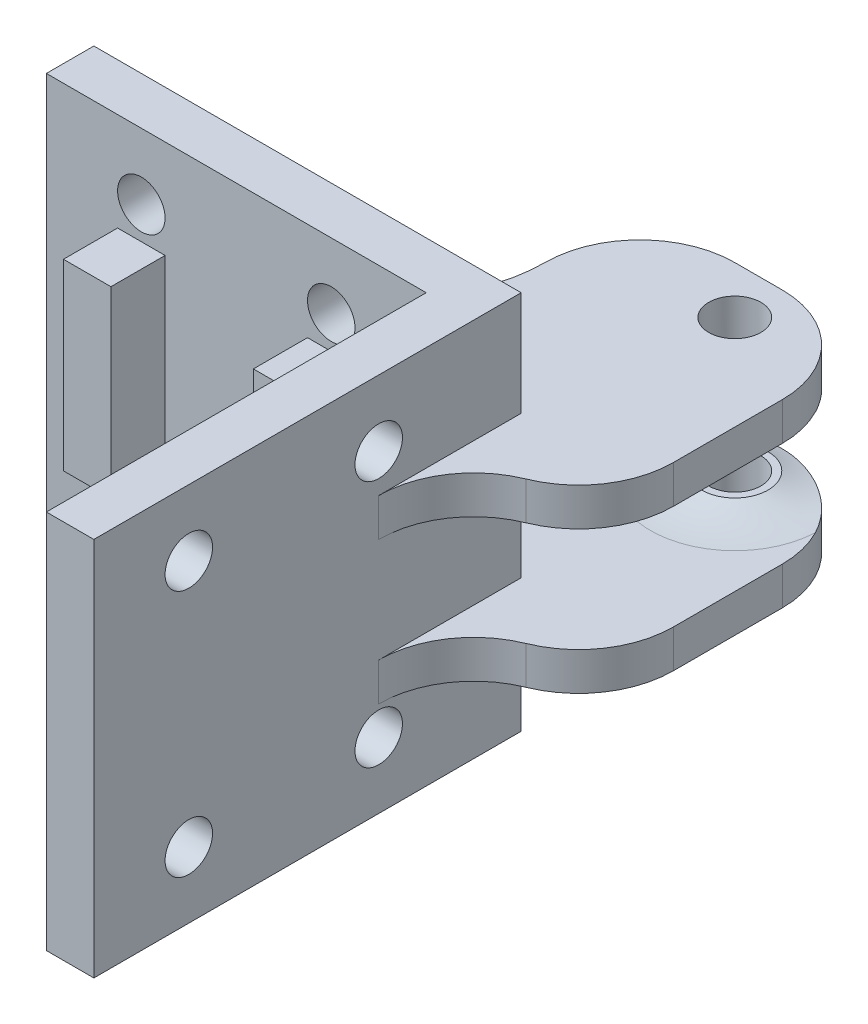
SolidWorks part; units mm, degrees
ref_plane "Alzado" through (0, 0, 0) normal (0, 0, 1) x (1, 0, 0)
ref_plane "Planta" through (0, 0, 0) normal (0, 1, 0) x (1, 0, 0)
ref_plane "Vista lateral" through (0, 0, 0) normal (1, 0, 0) x (0, 0, -1)
sketch "Croquis1" plane through (0, 0, 0) normal (0, 0, 1) x (1, 0, 0)
  line L1 (22.5, 20) -> (-22.5, 20)
  line L2 (22.5, 20) -> (22.5, -20)
  line L3 (22.5, -20) -> (-22.5, -20)
  line L4 (-22.5, 20) -> (-22.5, -20)
  line L5 (22.5, 20) -> (-22.5, -20) construction
  line L6 (22.5, -20) -> (-22.5, 20) construction
  point P0 (0, 0)
  dimension "D1" = 45
  dimension "D2" = 40
extrude "Saliente-Extruir1" add sketch "Croquis1" along normal blind 5
sketch "Croquis2" plane through (0, 0, 5) normal (0, 0, 1) x (1, 0, 0)
  line L0 (-22.5, -20) -> (22.5, -20) construction
  line L1 (22.5, 20) -> (17.5, 20)
  line L2 (22.5, 20) -> (22.5, -20)
  line L3 (22.5, -20) -> (17.5, -20)
  line L4 (17.5, 20) -> (17.5, -20)
  dimension "D1" = 5
extrude "Saliente-Extruir2" add sketch "Croquis2" along normal blind 40
sketch "Croquis23" plane through (0, -20, 0) normal (0, -1, 0) x (-1, 0, 0)
  line L0 (22.5, -5) -> (-17.5, -5) construction
  line L1 (10, -5) -> (15, -5)
  line L2 (10, -5) -> (10, -10.7)
  line L3 (10, -10.7) -> (15, -10.7)
  line L4 (15, -5) -> (15, -10.7)
  line L5 (10, -5) -> (15, -10.7) construction
  line L6 (10, -10.7) -> (15, -5) construction
  line L7 (-10, -10.7) -> (-5, -10.7)
  line L8 (-10, -10.7) -> (-10, -5)
  line L9 (-10, -5) -> (-5, -5)
  line L10 (-5, -10.7) -> (-5, -5)
  line L11 (-10, -10.7) -> (-5, -5) construction
  line L12 (-10, -5) -> (-5, -10.7) construction
  line L13 (22.5, -5) -> (22.5, 0) construction
  line L14 (-17.5, -45) -> (-17.5, -5) construction
  line L15 (-17.5, -32.5) -> (-11.8, -32.5)
  line L16 (-17.5, -32.5) -> (-17.5, -37.5)
  line L17 (-17.5, -37.5) -> (-11.8, -37.5)
  line L18 (-11.8, -32.5) -> (-11.8, -37.5)
  line L19 (-17.5, -32.5) -> (-11.8, -37.5) construction
  line L20 (-17.5, -37.5) -> (-11.8, -32.5) construction
  line L21 (-17.5, -12.5) -> (-11.8, -12.5)
  line L22 (-17.5, -12.5) -> (-17.5, -17.5)
  line L23 (-17.5, -17.5) -> (-11.8, -17.5)
  line L24 (-11.8, -12.5) -> (-11.8, -17.5)
  line L25 (-17.5, -12.5) -> (-11.8, -17.5) construction
  line L26 (-17.5, -17.5) -> (-11.8, -12.5) construction
  line L28 (-17.5, -45) -> (-22.5, -45) construction
  point P0 (12.5, -7.85)
  point P5 (-7.5, -7.85)
  point P14 (-14.65, -35)
  point P19 (-14.65, -15)
  dimension "D1" = 10
  dimension "D2" = 20
  dimension "D3" = 5.7
  dimension "D4" = 5
  dimension "D5" = 5
  dimension "D6" = 5.7
  dimension "D7" = 20
  dimension "D8" = 10
  dimension "D9" = 5
  dimension "D10" = 5
extrude "Saliente-Extruir8" add sketch "Croquis23" against normal up to surface (40 mm away) up to face at (5.8333, 20, 16.6667)
sketch "Croquis20" plane through (0, 0, 5) normal (0, 0, 1) x (1, 0, 0)
  line L1 (-22.5, -20) -> (17.5, -20)
  line L2 (-22.5, -20) -> (-22.5, -9.65)
  line L3 (-22.5, -9.65) -> (17.5, -9.65)
  line L4 (17.5, -20) -> (17.5, -9.65)
  line L5 (-22.5, 9.65) -> (17.5, 9.65)
  line L6 (-22.5, 9.65) -> (-22.5, 20)
  line L7 (-22.5, 20) -> (17.5, 20)
  line L8 (17.5, 9.65) -> (17.5, 20)
  line L10 (-22.5, 20) -> (-22.5, -20) construction
  line L11 (17.5, 20) -> (17.5, -20) construction
  line L13 (5, 20) -> (-10, 20) construction
  line L14 (-10, -20) -> (5, -20) construction
  dimension "D1" = 10.35
  dimension "D3" = 10.35
extrude "Cortar-Extruir4" cut sketch "Croquis20" along normal through all
sketch "Croquis21" plane through (0, 0, 5) normal (0, 0, 1) x (1, 0, 0)
  line L0 (-22.5, 20) -> (-22.5, -20) construction
  line L1 (17.5, 20) -> (-22.5, 20) construction
  line L3 (-22.5, -20) -> (17.5, -20) construction
  circle A0 centre (-12.5, 13.05) radius 2.5
  circle A1 centre (7.5, 13.05) radius 2.5
  circle A2 centre (-12.5, -13.05) radius 2.5
  circle A3 centre (7.5, -13.05) radius 2.5
  dimension "D1" = 5
  dimension "D2" = 10
  dimension "D3" = 6.95
  dimension "D4" = 6.95
extrude "Cortar-Extruir5" cut sketch "Croquis21" against normal up to surface (5 mm away) up to face at (0, 0, 0)
sketch "Croquis22" plane through (17.5, 0, 0) normal (-1, 0, 0) x (0, 0, 1)
  line L0 (45, 20) -> (45, -20) construction
  line L1 (45, 20) -> (5, 20) construction
  line L2 (45, -20) -> (5, -20) construction
  circle A0 centre (15, 13.05) radius 2.5
  circle A1 centre (35, 13.05) radius 2.5
  circle A2 centre (15, -13.05) radius 2.5
  circle A3 centre (35, -13.05) radius 2.5
  dimension "D1" = 5
  dimension "D2" = 10
  dimension "D3" = 6.95
  dimension "D4" = 20
  dimension "D5" = 6.95
extrude "Cortar-Extruir6" cut sketch "Croquis22" against normal up to surface (5 mm away) up to face at (22.5, 0, 22.5)
sketch "Croquis24" plane through (22.5, 0, 0) normal (1, 0, 0) x (0, 0, -1)
  line L0 (-45, 20) -> (0, 20) construction
  line L1 (25, 5) -> (-5, 5)
  line L2 (25, 5) -> (25, 9)
  line L3 (25, 9) -> (-5, 9)
  line L4 (-5, 5) -> (-5, 9)
  line L5 (25, -10) -> (-5, -10)
  line L6 (25, -10) -> (25, -6)
  line L7 (25, -6) -> (-5, -6)
  line L8 (-5, -10) -> (-5, -6)
  line L10 (-45, -20) -> (-45, 20) construction
  dimension "D1" = 30
  dimension "D2" = 40
  dimension "D3" = 11
  dimension "D4" = 11
  dimension "D5" = 4
  dimension "D6" = 4
extrude "Saliente-Extruir9" add sketch "Croquis24" along normal mid plane 25
fillet "Redondeo3" radius 10 1 edges at (22.5, -8, 5)
fillet "Redondeo4" radius 10 1 edges at (22.5, 7, 5)
sketch "Croquis25" plane through (0, -10, 0) normal (0, -1, 0) x (1, 0, 0)
  line L0 (35, 5) -> (35, -25) construction
  line L1 (-22.5, 0) -> (22.5, 0) construction
  circle A0 centre (25, -20) radius 2.75
  dimension "D1" = 5.5
  dimension "D2" = 10
  dimension "D3" = 20
extrude "Cortar-Extruir8" cut sketch "Croquis25" against normal through all
fillet "Redondeo5" radius 10 1 edges at (35, -8, 5)
fillet "Redondeo6" radius 10 3 edges at (35, 7, 5) (35, 7, -25) (35, -8, -25)
fillet "Redondeo7" radius 15 2 edges at (10, -8, 0) (10, 7, 0)
sketch "Croquis26" plane through (0, -6, 0) normal (0, 1, 0) x (1, 0, 0)
  circle A2 centre (25, 20) radius 3.5
  circle A3 centre (25, 20) radius 2.75
  dimension "D1" = 7
extrude "Saliente-Extruir10" add sketch "Croquis26" along normal blind 1
fillet "Redondeo8" radius 15 1 edges at (28.5, -6, -20)
sketch "Croquis27" plane through (0, 5, 0) normal (0, -1, 0) x (-1, 0, 0)
  circle A0 centre (-25, 20) radius 3.5
  circle A1 centre (-25, 20) radius 2.75
  dimension "D1" = 7
extrude "Saliente-Extruir11" add sketch "Croquis27" along normal blind 1
fillet "Redondeo9" radius 15 1 edges at (21.5, 5, -20)
fillet "Fillet1" radius 10 1 edges at (10, -8, -25)
fillet "Fillet2" radius 10 1 edges at (10, 7, -25)
